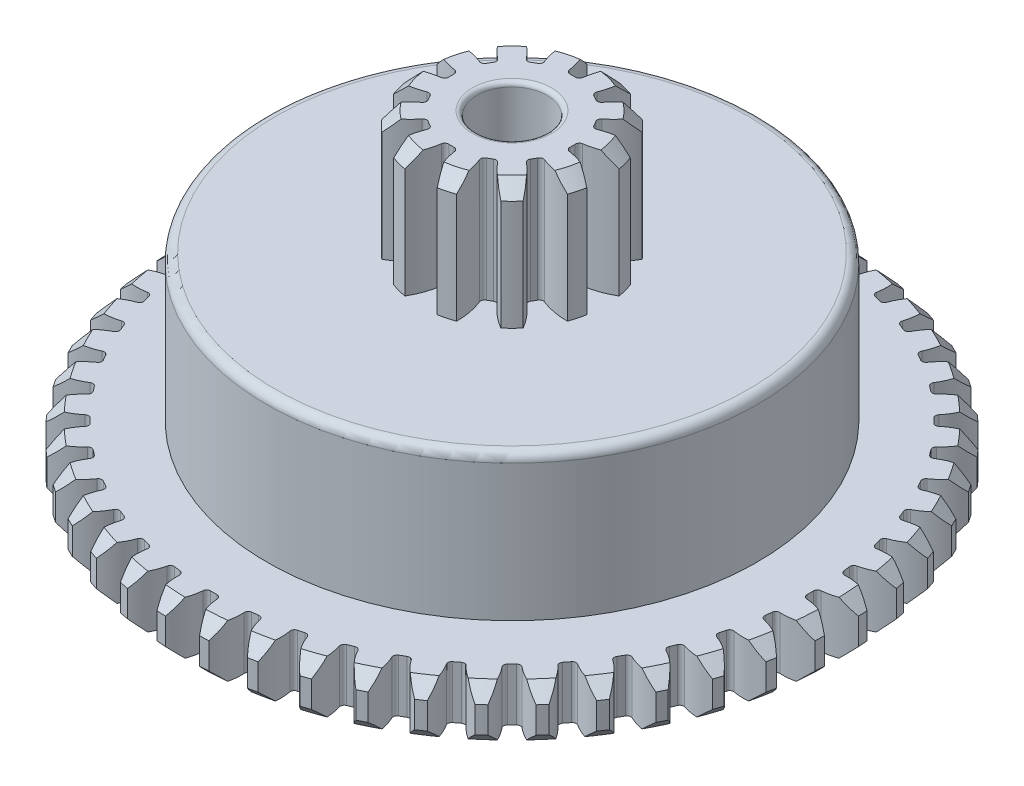
SolidWorks part; units mm, degrees
ref_plane "Front Plane" through (0, 0, 0) normal (0, 0, 1) x (1, 0, 0)
ref_plane "Top Plane" through (0, 0, 0) normal (0, 1, 0) x (1, 0, 0)
ref_plane "Right Plane" through (0, 0, 0) normal (1, 0, 0) x (0, 0, -1)
sketch "Sketch1" plane through (0, 0, 0) normal (0, 1, 0) x (1, 0, 0)
  circle A0 centre (0, 0) radius 1.8 construction
  circle A1 centre (0, 0) radius 2.1
  dimension "D1" = 3.6
  dimension "D2" = 4.2
extrude "Boss-Extrude1" add sketch "Sketch1" along normal blind 2.8
sketch "Sketch2" plane through (0, 2.8, 0) normal (0, 1, 0) x (1, 0, 0)
  line L0 (0, 0) -> (0, 2.1) construction
  line L1 (0, 0) -> (1.05, 1.8187) construction
  line L2 (0, 0) -> (0.5435, 2.0284) construction
  line L3 (-0.1405, 1.3728) -> (0, 0) construction
  line L4 (-0.2349, 1.7846) -> (0.2349, 1.7846) construction
  line L5 (0.2349, 1.7846) -> (0.6888, 1.663) construction
  line L6 (-0.3397, 2.0723) -> (0, 1.1391) construction
  circle A1 centre (0, 0) radius 1.5 construction
  circle A2 centre (0, 0) radius 2.1 construction
  arc A3 (-0.1405, 1.3728) -> (-0.3683, 2.0675) centre (-1.8457, 1.1983) ccw
  arc A4 (0.1405, 1.3728) -> (0.3683, 2.0675) centre (1.8457, 1.1983) cw
  circle A5 centre (0, 0) radius 1.8 construction
  arc A7 (0.1405, 1.3728) -> (-0.1405, 1.3728) centre (0, 0) ccw
  arc A8 (0.3683, 2.0675) -> (-0.3683, 2.0675) centre (0, 0) ccw
  dimension "D1" = 30
  dimension "D4" = 20
extrude "Cut-Extrude1" cut sketch "Sketch2" against normal up to next
fillet "Fillet1" radius 0.09 2 edges at (0.1405, 1.4, -1.3728) (-0.1405, 1.4, -1.3728)
chamfer "Chamfer1" distance 0.3 1 edges at (0, 2.8, 2.1)
pattern_circular "CirPattern1" count 12 over 360 about axis through (0, 2.8, 0) along (0, -1, 0) of "Cut-Extrude1", "Fillet1"
sketch "Sketch3" plane through (0, 0, 0) normal (0, -1, 0) x (1, 0, 0)
  circle A0 centre (0, 0) radius 5.575
  dimension "D1" = 11.15
extrude "Boss-Extrude2" add sketch "Sketch3" along normal blind 3.3
fillet "Fillet2" radius 0.2 1 edges at (0, 0, -5.575)
sketch "Sketch4" plane through (0, -3.3, 0) normal (0, -1, 0) x (1, 0, 0)
  circle A0 centre (0, 0) radius 7.2 construction
  circle A1 centre (0, 0) radius 7.5
  dimension "D1" = 14.4
  dimension "D2" = 15
extrude "Boss-Extrude3" add sketch "Sketch4" along normal blind 1.2
sketch "Sketch5" plane through (0, -4.5, 0) normal (0, -1, 0) x (1, 0, 0)
  line L0 (0, 0) -> (0, 7.5) construction
  line L1 (0, 0) -> (0.4905, 7.4839) construction
  line L2 (0, 0) -> (0.9789, 7.4358) construction
  line L3 (-0.1569, 6.7782) -> (0, 0) construction
  line L4 (-0.2356, 7.1961) -> (0.2356, 7.1961) construction
  line L5 (0.2356, 7.1961) -> (0.7057, 7.1653) construction
  line L6 (-0.3433, 7.4921) -> (0, 6.5489) construction
  arc A0 (0.4513, 6.8852) -> (-0.1652, 6.898) centre (0, 0) ccw construction
  circle A2 centre (0, 0) radius 7.5 construction
  arc A3 (-0.1569, 6.7782) -> (-0.3869, 7.49) centre (-1.4672, 6.7479) ccw
  arc A4 (0.1569, 6.7782) -> (0.3869, 7.49) centre (1.4672, 6.7479) cw
  circle A5 centre (0, 0) radius 7.2 construction
  arc A6 (0.3869, 7.49) -> (-0.3869, 7.49) centre (0, 0) ccw
  arc A7 (0.1569, 6.7782) -> (-0.1569, 6.7782) centre (0, 0) ccw
  dimension "D4" = 20
  dimension "D1" = 7.5
extrude "Cut-Extrude2" cut sketch "Sketch5" against normal up to next
fillet "Fillet3" radius 0.09 2 edges at (0.1569, -3.9, 6.7782) (-0.1569, -3.9, 6.7782)
chamfer "Chamfer2" distance 0.3 2 edges at (0, -3.3, -7.5) (0, -4.5, -7.5)
pattern_circular "CirPattern2" count 48 over 360 about axis through (0, -4.5, 0) along (0, 1, 0) of "Cut-Extrude2", "Fillet3"
sketch "Sketch6" plane through (0, -4.5, 0) normal (0, -1, 0) x (1, 0, 0)
  circle A0 centre (0, 0) radius 4.5
  circle A1 centre (0, 0) radius 7.5 construction
  dimension "D1" = 3
extrude "Cut-Extrude3" cut sketch "Sketch6" against normal blind 3.4
sketch "Sketch7" plane through (0, 2.8, 0) normal (0, 1, 0) x (1, 0, 0)
  circle A0 centre (0, 0) radius 0.8
  dimension "D1" = 1.6
extrude "Cut-Extrude4" cut sketch "Sketch7" against normal through all
fillet "Fillet4" radius 0.1 2 edges at (0, 2.8, 0.8) (0, -4.5, -4.5)
equation "\"Module of small gear\"= 0.3"
equation "\"Number of teeth of small gear\"= 12"
equation "\"Pressure Angle\"= 20"
equation "\"D1@Sketch1\"=\"Module of small gear\" * \"Number of teeth of small gear\""
equation "\"D2@Sketch1\"=(\"Number of teeth of small gear\" + 2) * \"Module of small gear\""
equation "\"D1@Sketch2\"=360 / \"Number of teeth of small gear\""
equation "\"D2@Sketch2\"=\"Module of small gear\" * 2"
equation "\"D4@Sketch2\"=\"Pressure Angle\""
equation "\"D1@Chamfer1\"=\"Module of small gear\""
equation "\"D1@Fillet1\"=0.3 * \"Module of small gear\""
equation "\"D1@CirPattern1\"=\"Number of teeth of small gear\""
equation "\"Module of big gear\"= 0.3"
equation "\"Number of teeth of big gear\"= 48"
equation "\"D1@Sketch4\"=\"Module of big gear\" * \"Number of teeth of big gear\""
equation "\"D2@Sketch4\"=(\"Number of teeth of big gear\" + 2) * \"Module of big gear\""
equation "\"D1@Sketch5\"=360 / \"Number of teeth of big gear\""
equation "\"D2@Sketch5\"=\"Module of big gear\" * 2"
equation "\"D4@Sketch5\"=\"Pressure Angle\""
equation "\"D1@Fillet3\"=0.3 * \"Module of big gear\""
equation "\"D1@Chamfer2\"=\"Module of big gear\""
equation "\"D1@CirPattern2\"=\"Number of teeth of big gear\""
